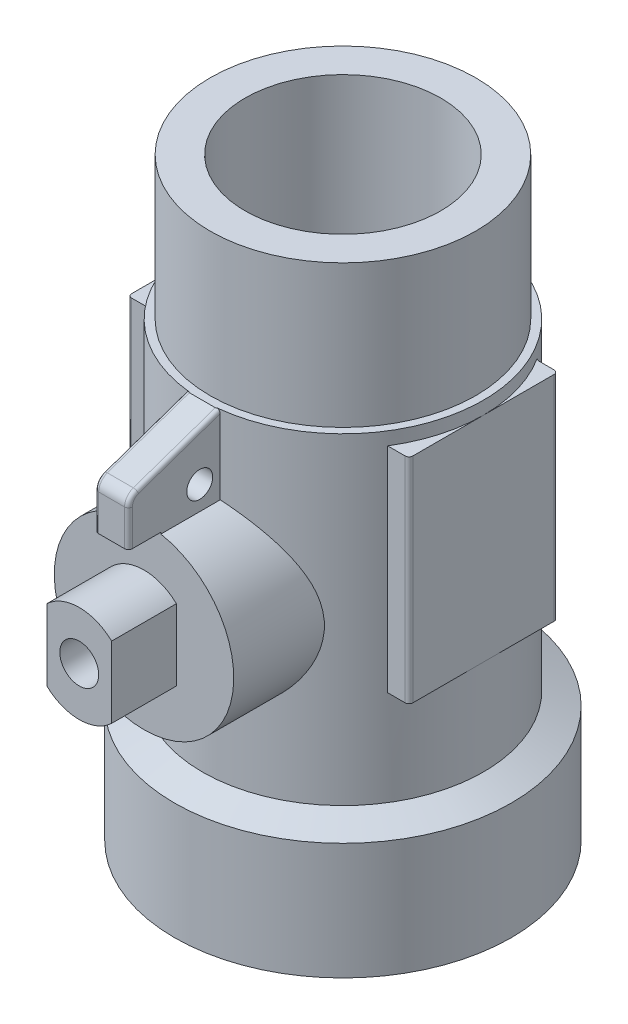
SolidWorks part; units mm, degrees
material "Brass"
ref_plane "Front Plane" through (0, 0, 0) normal (0, 0, 1) x (1, 0, 0)
ref_plane "Top Plane" through (0, 0, 0) normal (0, 1, 0) x (1, 0, 0)
ref_plane "Right Plane" through (0, 0, 0) normal (1, 0, 0) x (0, 0, -1)
sketch "Sketch1" plane through (0, 0, 0) normal (0, 0, 1) x (1, 0, 0)
  line L0 (0, 0) -> (0, 45.85) construction
  line L1 (0, 45.85) -> (7.55, 45.85) construction
  line L2 (7.55, 45.85) -> (7.55, 33.85)
  line L3 (7.55, 33.85) -> (5, 32.85)
  line L4 (5, 32.85) -> (5, 28.85)
  line L5 (5, 28.85) -> (0, 28.85)
  line L6 (0, 28.85) -> (0, 12)
  line L7 (0, 12) -> (5, 12)
  line L8 (5, 12) -> (5, 7.7)
  line L9 (5, 7.7) -> (9, 7.7)
  line L10 (9, 7.7) -> (9, 0)
  line L11 (9, 0) -> (13, 0)
  line L12 (13, 0) -> (13, 9)
  line L13 (13, 9) -> (10.85, 10)
  line L16 (10.85, 10) -> (10.85, 34.85)
  line L20 (10.25, 34.85) -> (10.25, 45.85)
  line L21 (10.25, 45.85) -> (7.55, 45.85)
  line L22 (10.85, 34.85) -> (10.25, 34.85)
  dimension "D1" = 45.85
  dimension "D2" = 12
  dimension "D3" = 13
  dimension "D4" = 17
  dimension "D5" = 10.25
  dimension "D6" = 2.7
  dimension "D7" = 5
  dimension "D8" = 11
  dimension "D9" = 8
  dimension "D10" = 1
  dimension "D11" = 13
  dimension "D12" = 4
  dimension "D14" = 7.7
  dimension "D15" = 12
  dimension "D16" = 10.85
  dimension "D17" = 9
revolve "Revolve1" add sketch "Sketch1" angle 360 about L0
ref_plane "Plane1" through (10.85, 0, 0) normal (1, 0, 0) x (0, 1, 0)
sketch "Sketch2" plane through (10.85, 0, 0) normal (1, 0, 0) x (0, 1, 0)
  line L1 (33.85, 5.75) -> (17.35, 5.75)
  line L2 (33.85, 5.75) -> (33.85, -5.75)
  line L3 (33.85, -5.75) -> (17.35, -5.75)
  line L4 (17.35, 5.75) -> (17.35, -5.75)
  line L5 (34.85, -10.85) -> (34.85, 10.85) construction
  point P12 (17.35, 0)
  dimension "D1" = 1
  dimension "D2" = 16.5
  dimension "D3" = 11.5
extrude "Boss-Extrude1" add sketch "Sketch2" against normal blind 2
mirror "Mirror1" about plane through (0, 0, 0) normal (1, 0, 0) of "Boss-Extrude1"
ref_plane "Plane2" through (0, 0, 10.85) normal (0, 0, 1) x (0, -1, 0)
sketch "Sketch3" plane through (0, 0, 10.85) normal (0, 0, 1) x (0, -1, 0)
  line L0 (0, -13) -> (0, 13) construction
  circle A0 centre (-22, 0) radius 6.925
  dimension "D1" = 13.85
  dimension "D2" = 22
extrude "Boss-Extrude2" add sketch "Sketch3" along normal blind 4.5 and the other way blind 3
sketch "Sketch4" plane through (0, 0, 0) normal (1, 0, 0) x (0, 0, -1)
  line L12 (-10.85, 34.85) -> (-17.85, 32.425)
  line L13 (-17.85, 32.425) -> (-17.85, 28.925)
  line L14 (-17.85, 28.925) -> (-15.35, 28.925)
  line L15 (-15.35, 28.925) -> (-15.35, 27.925)
  line L16 (-15.35, 27.925) -> (-10.25, 27.925)
  line L20 (-10.85, 34.85) -> (-10.25, 34.85)
  line L21 (-10.25, 34.85) -> (-10.25, 27.925)
  line L23 (10.85, 34.85) -> (-10.85, 34.85) construction
  line L24 (10.25, 34.85) -> (-10.25, 34.85) construction
  circle A0 centre (-12.35, 30.625) radius 1
  dimension "D6" = 2
  dimension "D1" = 2.5
  dimension "D2" = 3.5
  dimension "D3" = 1
  dimension "D4" = 2.7
  dimension "D5" = 2.1
extrude "Boss-Extrude6" add sketch "Sketch4" along normal blind 1.3 and the other way blind 1.3
fillet "Fillet2" radius 0.3 1 edges at (-9.2011, 25.6, 5.75)
fillet "Fillet4" radius 0.3 1 edges at (10.85, 25.6, 5.75)
fillet "Fillet7" radius 0.3 1 edges at (10.85, 25.6, -5.75)
fillet "Fillet8" radius 0.3 1 edges at (-10.85, 25.6, -5.75)
fillet "Fillet9" radius 0.3 1 edges at (-10.85, 25.6, 5.75)
fillet "Fillet10" radius 0.3 4 edges at (1.3, 30.675, 17.85) (-1.3, 33.6375, 14.35) (-1.3, 30.675, 17.85) (1.3, 33.6375, 14.35)
fillet "Fillet11" radius 0.3 1 edges at (9.2011, 25.6, -5.75)
fillet "Fillet12" radius 0.3 1 edges at (-9.2011, 25.6, -5.75)
sketch "Sketch5" plane through (0, 0, 15.35) normal (0, 0, 1) x (1, 0, 0)
  line L0 (-2.5, 19.25) -> (-2.5, 24.75)
  line L1 (2.5, 19.25) -> (2.5, 24.75)
  line L2 (-6.925, 22) -> (6.925, 22) construction
  line L3 (0, 15.075) -> (0, 28.925) construction
  line L4 (-1.3, 28.925) -> (1.3, 28.925) construction
  arc A0 (-2.5, 19.25) -> (2.5, 19.25) centre (0, 21.875) ccw
  arc A1 (-2.5, 24.75) -> (2.5, 24.75) centre (0, 22.125) cw
  circle A2 centre (0, 22) radius 1.5
  arc A3 (-1.3, 28.8019) -> (1.3, 28.8019) centre (0, 22) ccw construction
  point P6 (0, 18.25)
  point P7 (0, 25.75)
  point P14 (-2.5, 22)
  point P15 (2.5, 22)
  dimension "D4" = 3
  dimension "D1" = 5.5
  dimension "D2" = 7.5
  dimension "D3" = 5
extrude "Boss-Extrude7" add sketch "Sketch5" along normal blind 5
fillet "Fillet13" radius 1 3 edges at (1.2121, 32.3624, 17.7621) (-1.2121, 32.3624, 17.7621) (0, 32.425, 17.85)
